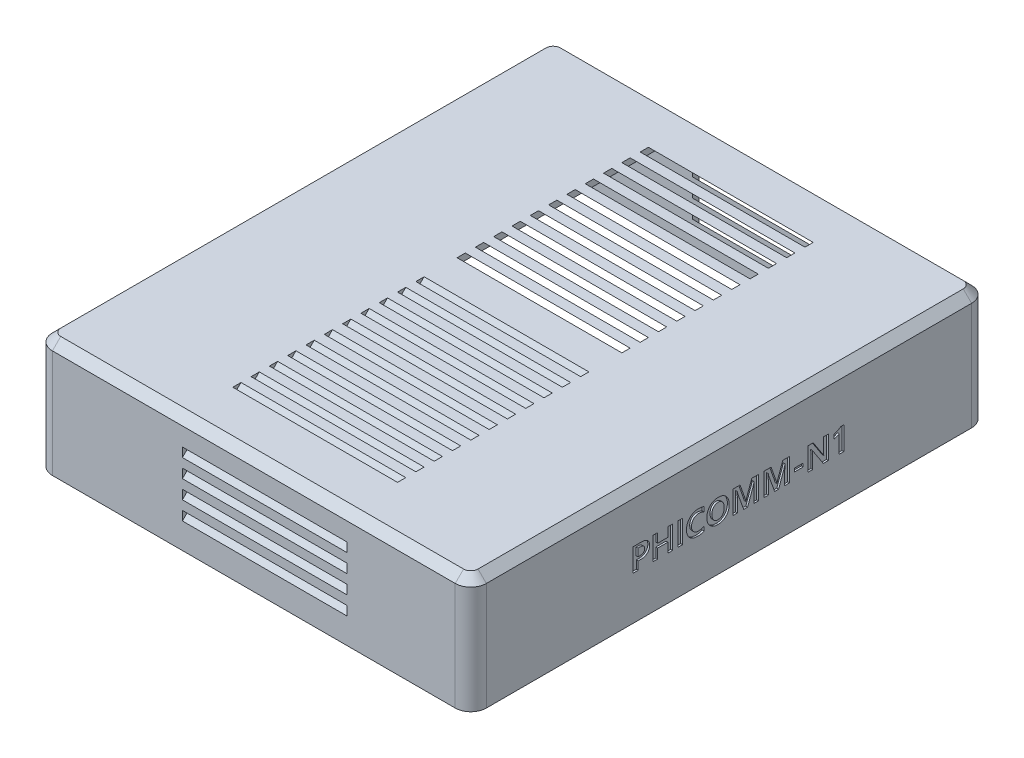
SolidWorks part; units mm, degrees
ref_plane "前视基准面" through (0, 0, 0) normal (0, 0, 1) x (1, 0, 0)
ref_plane "上视基准面" through (0, 0, 0) normal (0, 1, 0) x (1, 0, 0)
ref_plane "右视基准面" through (0, 0, 0) normal (1, 0, 0) x (0, 0, -1)
sketch "草图1" plane through (0, 0, 0) normal (0, 1, 0) x (1, 0, 0)
  line L1 (-46, -55) -> (46, -55)
  line L2 (-46, -55) -> (-46, 55)
  line L3 (-46, 55) -> (46, 55)
  line L4 (46, -55) -> (46, 55)
  line L5 (-46, -55) -> (46, 55) construction
  line L6 (-46, 55) -> (46, -55) construction
  point P0 (0, 0)
  dimension "D1" = 110
  dimension "D2" = 92
extrude "凸台-拉伸1" add sketch "草图1" along normal blind 24
fillet "圆角1" radius 2 4 edges at (-46, 12, -55) (46, 12, -55) (46, 12, 55) (-46, 12, 55)
chamfer "倒角1" distance 1 angle 45 8 edges at (45.4142, 24, -54.4142) (46, 24, 0) (45.4142, 24, 54.4142) (0, 24, 55) (-45.4142, 24, 54.4142) (-46, 24, 0) (-45.4142, 24, -54.4142) (0, 24, -55)
shell "抽壳1" thickness 1.4 removed face at (0, 0, 0) outward yes
sketch "草图2" plane through (0, 25.4, 0) normal (0, 1, 0) x (-1, 0, 0)
  line L0 (-37.25, 40.5) -> (-37.25, -51.5) construction
  line L5 (-45, 53) -> (-45, -53) construction
  line L6 (-44, -54) -> (44, -54) construction
  circle A0 centre (-37.25, 40.5) radius 0.75
  circle A1 centre (-37.25, -51.5) radius 0.75
  circle A2 centre (-37.25, 40.5) radius 2.75
  circle A3 centre (-37.25, -51.5) radius 2.75
  dimension "D1" = 1.5
  dimension "D2" = 5.5
  dimension "D3" = 92
  dimension "D4" = 7.75
  dimension "D5" = 2.5
extrude "凸台-拉伸2" add sketch "草图2" against normal blind 17.5
chamfer "倒角2" distance 1.5 angle 45 2 edges at (37.25, 24, -48.75) (37.25, 24, 37.75)
sketch "草图6" plane through (0, 24, 0) normal (0, -1, 0) x (1, 0, 0)
  line L0 (46, 53) -> (46, -53) construction
  line L1 (38, 41.5) -> (46, 41.5)
  line L2 (38, 41.5) -> (38, 39.5)
  line L3 (38, 39.5) -> (46, 39.5)
  line L4 (46, 41.5) -> (46, 39.5)
  line L5 (36.25, -52.25) -> (38.25, -52.25)
  line L6 (36.25, -52.25) -> (36.25, -55)
  line L7 (36.25, -55) -> (38.25, -55)
  line L8 (38.25, -52.25) -> (38.25, -55)
  line L9 (-44, -55) -> (44, -55) construction
  circle A0 centre (37.25, 40.5) radius 0.75 construction
  circle A3 centre (37.25, -51.5) radius 0.75 construction
  point P8 (37.25, -51.5)
  point P13 (37.25, -52.25)
  point P17 (38, 40.5)
  point P25 (37.25, 40.5)
  dimension "D1" = 2
extrude "凸台-拉伸4" add sketch "草图6" along normal up to surface (16.1 mm away) up to face at (37.25, 7.9, -50.75)
sketch "草图3" plane through (-47.4, 0, 0) normal (-1, 0, 0) x (0, 0, 1)
  line L0 (-25.575, 4.8) -> (-32.175, 4.8)
  line L1 (-32.175, 4.8) -> (-32.175, 7.4)
  line L2 (-32.175, 7.4) -> (-35.05, 7.4)
  line L3 (-35.05, 7.4) -> (-35.05, 14.75)
  line L4 (-35.05, 14.75) -> (-22.7, 14.75)
  line L5 (-22.7, 14.75) -> (-22.7, 7.4)
  line L6 (-22.7, 7.4) -> (-25.575, 7.4)
  line L7 (-25.575, 7.4) -> (-25.575, 4.8)
  line L8 (-17.8, 13.84) -> (-3.3, 13.84)
  line L9 (-3.3, 13.84) -> (-3.3, 10.589)
  line L10 (-3.3, 10.589) -> (-4.8, 8.94)
  line L11 (-4.8, 8.94) -> (-16.3, 8.94)
  line L12 (-16.3, 8.94) -> (-17.8, 10.589)
  line L13 (-17.8, 10.589) -> (-17.8, 13.84)
  line L15 (2.8, 15.2) -> (16, 15.2)
  line L16 (2.8, 15.2) -> (2.8, 9.5)
  line L17 (2.8, 9.5) -> (16, 9.5)
  line L18 (16, 15.2) -> (16, 9.5)
  line L28 (49.3, 9.7) -> (36.9, 9.7)
  line L29 (36.9, 9.7) -> (36.9, 17.05)
  line L31 (49.3, 17.05) -> (49.3, 9.7)
  line L34 (36.9, 17.05) -> (39.8, 17.05)
  line L35 (39.8, 17.05) -> (39.8, 19.65)
  line L36 (39.8, 19.65) -> (46.4, 19.65)
  line L37 (46.4, 19.65) -> (46.4, 17.05)
  line L38 (46.4, 17.05) -> (49.3, 17.05)
  line L41 (37.75, 7.9) -> (43.25, 7.9) construction
  line L42 (55, 23) -> (55, 0) construction
  circle A0 centre (-42.45, 11.75) radius 3.05
  dimension "D10" = 6.1
  dimension "D15" = 45.25
  dimension "D1" = 13.2
  dimension "D2" = 5.7
  dimension "D3" = 4.9
  dimension "D4" = 14.5
  dimension "D5" = 11.5
  dimension "D6" = 12.35
  dimension "D7" = 9.95
  dimension "D8" = 6.6
  dimension "D9" = 7.35
  dimension "D11" = 1.36
  dimension "D12" = 0.45
  dimension "D13" = 6.1
  dimension "D14" = 25.5
  dimension "D16" = 12.4
  dimension "D17" = 6.6
  dimension "D18" = 9.95
  dimension "D19" = 7.35
  dimension "D20" = 0.2
  dimension "D21" = 34.1
  dimension "D22" = 1.6
  dimension "D23" = 39
  dimension "D24" = 3.45
extrude "切除-拉伸1" cut sketch "草图3" against normal blind 14
sketch "草图4" plane through (-46, 0, 0) normal (1, 0, 0) x (0, 0, -1)
  line L0 (-53, 24) -> (53, 24) construction
  line L1 (31.375, 24) -> (26.375, 24)
  line L2 (31.375, 24) -> (31.375, 16.75)
  line L3 (31.375, 16.75) -> (26.375, 16.75)
  line L4 (26.375, 24) -> (26.375, 16.75)
  line L5 (22.7, 14.75) -> (35.05, 14.75) construction
  line L6 (-6.9, 24) -> (-11.9, 24)
  line L7 (-6.9, 24) -> (-6.9, 15.4)
  line L8 (-6.9, 15.4) -> (-11.9, 15.4)
  line L9 (-11.9, 24) -> (-11.9, 15.4)
  line L10 (-16, 15.2) -> (-2.8, 15.2) construction
  line L12 (-53, 24) -> (-41.5, 24) construction
  point P10 (28.875, 16.75)
  point P13 (28.875, 14.75)
  point P14 (-9.4, 15.4)
  point P17 (-9.4, 15.2)
  dimension "D1" = 5
  dimension "D2" = 2
  dimension "D3" = 0.2
extrude "凸台-拉伸3" add sketch "草图4" along normal blind 8
sketch "草图8" plane through (-46, 0, 0) normal (1, 0, 0) x (0, 0, -1)
  line L0 (-43.25, 7.9) -> (-37.75, 7.9) construction
  line L1 (47.5, 6.5) -> (44, 6.5)
  line L2 (47.5, 6.5) -> (47.5, 4)
  line L3 (47.5, 4) -> (44, 4)
  line L4 (44, 6.5) -> (44, 4)
  line L5 (-28, 6.5) -> (-31.5, 6.5)
  line L6 (-28, 6.5) -> (-28, 4)
  line L7 (-28, 4) -> (-31.5, 4)
  line L8 (-31.5, 6.5) -> (-31.5, 4)
  line L12 (-16, 9.5) -> (-16, 15.2) construction
  line L13 (53, 0) -> (-53, 0) construction
  line L18 (2, 0) -> (-2, 0)
  line L19 (2, 0) -> (2, 2)
  line L20 (2, 2) -> (-2, 2)
  line L21 (-2, 0) -> (-2, 2)
  line L22 (42, 0) -> (42, 2)
  line L23 (42, 2) -> (38, 2)
  line L24 (38, 0) -> (38, 2)
  line L25 (42, 0) -> (38, 0)
  line L26 (-38, 0) -> (-38, 2)
  line L27 (-38, 2) -> (-42, 2)
  line L28 (-42, 0) -> (-42, 2)
  line L29 (-38, 0) -> (-42, 0)
  point P16 (0, 2)
  dimension "D1" = 3.5
  dimension "D2" = 1.4
  dimension "D3" = 12
  dimension "D4" = 2.5
  dimension "D5" = 60
  dimension "D6" = 4
  dimension "D7" = 2
  dimension "D8" = 2
  dimension "D9" = 2
extrude "凸台-拉伸6" add sketch "草图8" along normal blind 2.5
chamfer "倒角3" distance 2 angle 45 4 edges at (-46, 5.25, 31.5) (-46, 5.25, 28) (-46, 5.25, -47.5) (-46, 5.25, -44)
chamfer "倒角4" distance 1.2 angle 45 3 edges at (-43.5, 2, 40) (-43.5, 2, 0) (-43.5, 2, -40)
ref_plane "基准面1" through (20.4, 0, 0) normal (1, 0, 0) x (0, 0, -1)
sketch "草图9" plane through (20.4, 0, 0) normal (1, 0, 0) x (0, 0, -1)
  line L0 (-5.4, 25.4) -> (-6.8, 24)
  line L1 (-5.4, 25.4) -> (-3.6, 25.4)
  line L2 (-6.8, 24) -> (-5, 24)
  line L3 (-3.6, 25.4) -> (-5, 24)
  line L4 (-53, 25.4) -> (53, 25.4) construction
  line L5 (-53, 24) -> (-41.5, 24) construction
  line L8 (0, 0) -> (0, 38.023) construction
  line L9 (-7.6, 25.4) -> (-9, 24)
  line L10 (-9.4, 25.4) -> (-7.6, 25.4)
  line L11 (-9.4, 25.4) -> (-10.8, 24)
  line L12 (-10.8, 24) -> (-9, 24)
  line L13 (-11.6, 25.4) -> (-13, 24)
  line L14 (-13.4, 25.4) -> (-11.6, 25.4)
  line L15 (-13.4, 25.4) -> (-14.8, 24)
  line L16 (-14.8, 24) -> (-13, 24)
  line L17 (-15.6, 25.4) -> (-17, 24)
  line L18 (-17.4, 25.4) -> (-15.6, 25.4)
  line L19 (-17.4, 25.4) -> (-18.8, 24)
  line L20 (-18.8, 24) -> (-17, 24)
  line L21 (-19.6, 25.4) -> (-21, 24)
  line L22 (-21.4, 25.4) -> (-19.6, 25.4)
  line L23 (-21.4, 25.4) -> (-22.8, 24)
  line L24 (-22.8, 24) -> (-21, 24)
  line L25 (-23.6, 25.4) -> (-25, 24)
  line L26 (-25.4, 25.4) -> (-23.6, 25.4)
  line L27 (-25.4, 25.4) -> (-26.8, 24)
  line L28 (-26.8, 24) -> (-25, 24)
  line L29 (-27.6, 25.4) -> (-29, 24)
  line L30 (-29.4, 25.4) -> (-27.6, 25.4)
  line L31 (-29.4, 25.4) -> (-30.8, 24)
  line L32 (-30.8, 24) -> (-29, 24)
  line L33 (-31.6, 25.4) -> (-33, 24)
  line L34 (-33.4, 25.4) -> (-31.6, 25.4)
  line L35 (-33.4, 25.4) -> (-34.8, 24)
  line L36 (-34.8, 24) -> (-33, 24)
  line L37 (-35.6, 25.4) -> (-37, 24)
  line L38 (-37.4, 25.4) -> (-35.6, 25.4)
  line L39 (-37.4, 25.4) -> (-38.8, 24)
  line L40 (-38.8, 24) -> (-37, 24)
  line L41 (-39.6, 25.4) -> (-41, 24)
  line L42 (-41.4, 25.4) -> (-39.6, 25.4)
  line L43 (-41.4, 25.4) -> (-42.8, 24)
  line L44 (-42.8, 24) -> (-41, 24)
  line L45 (-43.6, 25.4) -> (-45, 24)
  line L46 (-45.4, 25.4) -> (-43.6, 25.4)
  line L47 (-45.4, 25.4) -> (-46.8, 24)
  line L48 (-46.8, 24) -> (-45, 24)
  line L49 (46.8, 24) -> (45, 24)
  line L50 (45.4, 25.4) -> (46.8, 24)
  line L51 (45.4, 25.4) -> (43.6, 25.4)
  line L52 (43.6, 25.4) -> (45, 24)
  line L53 (42.8, 24) -> (41, 24)
  line L54 (41.4, 25.4) -> (42.8, 24)
  line L55 (41.4, 25.4) -> (39.6, 25.4)
  line L56 (39.6, 25.4) -> (41, 24)
  line L57 (38.8, 24) -> (37, 24)
  line L58 (37.4, 25.4) -> (38.8, 24)
  line L59 (37.4, 25.4) -> (35.6, 25.4)
  line L60 (35.6, 25.4) -> (37, 24)
  line L61 (34.8, 24) -> (33, 24)
  line L62 (33.4, 25.4) -> (34.8, 24)
  line L63 (33.4, 25.4) -> (31.6, 25.4)
  line L64 (31.6, 25.4) -> (33, 24)
  line L65 (30.8, 24) -> (29, 24)
  line L66 (29.4, 25.4) -> (30.8, 24)
  line L67 (29.4, 25.4) -> (27.6, 25.4)
  line L68 (27.6, 25.4) -> (29, 24)
  line L69 (26.8, 24) -> (25, 24)
  line L70 (25.4, 25.4) -> (26.8, 24)
  line L71 (25.4, 25.4) -> (23.6, 25.4)
  line L72 (23.6, 25.4) -> (25, 24)
  line L73 (22.8, 24) -> (21, 24)
  line L74 (21.4, 25.4) -> (22.8, 24)
  line L75 (21.4, 25.4) -> (19.6, 25.4)
  line L76 (19.6, 25.4) -> (21, 24)
  line L77 (18.8, 24) -> (17, 24)
  line L78 (17.4, 25.4) -> (18.8, 24)
  line L79 (17.4, 25.4) -> (15.6, 25.4)
  line L80 (15.6, 25.4) -> (17, 24)
  line L81 (14.8, 24) -> (13, 24)
  line L82 (13.4, 25.4) -> (14.8, 24)
  line L83 (13.4, 25.4) -> (11.6, 25.4)
  line L84 (11.6, 25.4) -> (13, 24)
  line L85 (10.8, 24) -> (9, 24)
  line L86 (9.4, 25.4) -> (10.8, 24)
  line L87 (9.4, 25.4) -> (7.6, 25.4)
  line L88 (7.6, 25.4) -> (9, 24)
  line L89 (3.6, 25.4) -> (5, 24)
  line L90 (6.8, 24) -> (5, 24)
  line L91 (5.4, 25.4) -> (3.6, 25.4)
  line L92 (5.4, 25.4) -> (6.8, 24)
  dimension "D1" = 45
  dimension "D2" = 1.8
  dimension "D3" = 5
  dimension "D4" = 11
extrude "切除-拉伸2" cut sketch "草图9" against normal blind 36
sketch "草图10" plane through (20.4, 0, 0) normal (1, 0, 0) x (0, 0, -1)
  line L0 (-55, 21) -> (-56.4, 19.6)
  line L1 (-55, 21) -> (-55, 19)
  line L2 (-56.4, 19.6) -> (-56.4, 17.6)
  line L3 (-55, 19) -> (-56.4, 17.6)
  line L4 (-55, 0) -> (-55, 23) construction
  line L5 (-56.4, 0) -> (-56.4, 23.5799) construction
  line L6 (-54, 24) -> (-53, 24) construction
  line L7 (0, 0) -> (0, 31.4647) construction
  line L8 (-53, 0) -> (53, 0) construction
  line L9 (-55, 17) -> (-56.4, 15.6)
  line L10 (-56.4, 15.6) -> (-56.4, 13.6)
  line L11 (-55, 17) -> (-55, 15)
  line L12 (-55, 15) -> (-56.4, 13.6)
  line L13 (-55, 13) -> (-56.4, 11.6)
  line L14 (-56.4, 11.6) -> (-56.4, 9.6)
  line L15 (-55, 13) -> (-55, 11)
  line L16 (-55, 11) -> (-56.4, 9.6)
  line L17 (-55, 9) -> (-56.4, 7.6)
  line L18 (-56.4, 7.6) -> (-56.4, 5.6)
  line L19 (-55, 9) -> (-55, 7)
  line L20 (-55, 7) -> (-56.4, 5.6)
  line L21 (55, 7) -> (56.4, 5.6)
  line L22 (55, 9) -> (55, 7)
  line L23 (56.4, 7.6) -> (56.4, 5.6)
  line L24 (55, 9) -> (56.4, 7.6)
  line L25 (55, 11) -> (56.4, 9.6)
  line L26 (55, 13) -> (55, 11)
  line L27 (56.4, 11.6) -> (56.4, 9.6)
  line L28 (55, 13) -> (56.4, 11.6)
  line L29 (55, 15) -> (56.4, 13.6)
  line L30 (55, 17) -> (55, 15)
  line L31 (56.4, 15.6) -> (56.4, 13.6)
  line L32 (55, 17) -> (56.4, 15.6)
  line L33 (55, 19) -> (56.4, 17.6)
  line L34 (56.4, 19.6) -> (56.4, 17.6)
  line L35 (55, 21) -> (55, 19)
  line L36 (55, 21) -> (56.4, 19.6)
  dimension "D1" = 2
  dimension "D2" = 3
  dimension "D3" = 45
  dimension "D4" = 4
extrude "切除-拉伸3" cut sketch "草图10" against normal up to surface (36 mm away) up to face at (-15.6, 24.7, -41.2)
sketch "草图11" plane through (47.4, 0, 0) normal (1, 0, 0) x (0, 0, -1)
  text T0 "PHICOMM-N1" font "微软雅黑" height 5
extrude "切除-拉伸4" cut sketch "草图11" against normal blind 0.4
